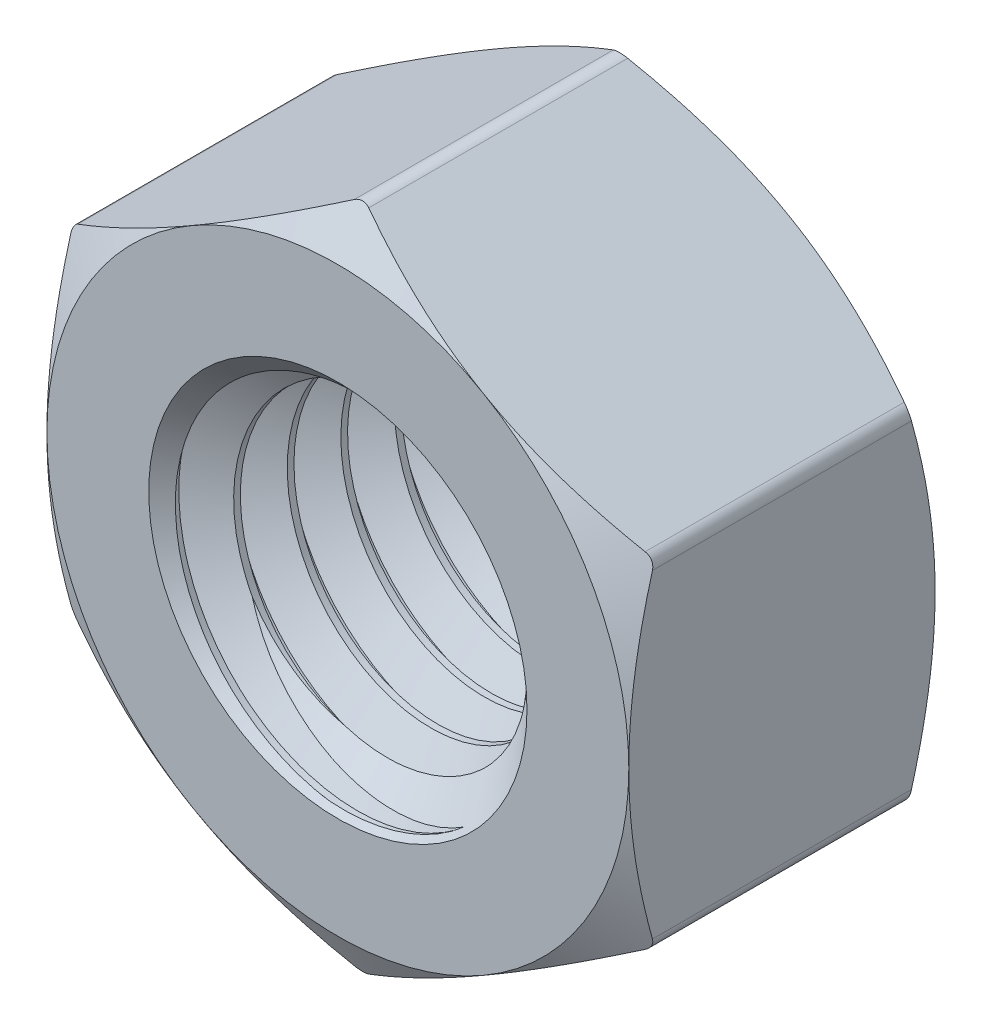
SolidWorks part; units mm, degrees
ref_plane "Front" through (0, 0, 0) normal (0, 0, 1) x (1, 0, 0)
ref_plane "Top" through (0, 0, 0) normal (0, 1, 0) x (1, 0, 0)
ref_plane "Right" through (0, 0, 0) normal (1, 0, 0) x (0, 0, -1)
sketch "Sketch1" plane through (0, 0, 0) normal (0, 0, 1) x (1, 0, 0)
  line L0 (0, 6) -> (0, 4.25) construction
  line L1 (-9.5, 5.4848) -> (-9.5, -5.4848)
  line L2 (-9.5, -5.4848) -> (0, -10.9697)
  line L3 (0, -10.9697) -> (9.5, -5.4848)
  line L4 (9.5, -5.4848) -> (9.5, 5.4848)
  line L5 (9.5, 5.4848) -> (0, 10.9697)
  line L6 (0, 10.9697) -> (-9.5, 5.4848)
  circle A0 centre (0, 0) radius 9.5 construction
  circle A1 centre (0, 0) radius 6 construction
  point P10 (0, 6)
  dimension "Width" = 19
  dimension "Thread Size" = 12
  dimension "Thread Pitch" = 1.75
sketch "Sketch2" plane through (0, 0, 0) normal (1, 0, 0) x (0, 0, -1)
  line L0 (-5, 0) -> (5, 0) construction
  line L1 (-5, 10.9697) -> (5, 10.9697) construction
  dimension "Height" = 10
sketch "Sketch15" plane through (0, 0, 0) normal (0, 0, 1) x (1, 0, 0)
  line L1 (0, 10.9697) -> (-9.5, 5.4848)
  line L2 (-9.5, 5.4848) -> (-9.5, -5.4848)
  line L3 (-9.5, -5.4848) -> (0, -10.9697)
  line L4 (0, -10.9697) -> (9.5, -5.4848)
  line L5 (9.5, -5.4848) -> (9.5, 5.4848)
  line L6 (9.5, 5.4848) -> (0, 10.9697)
  circle A0 centre (0, 0) radius 9.5 construction
extrude "Boss-Extrude2" add sketch "Sketch15" along normal mid plane 10
sketch "Sketch16" plane through (0, 0, 0) normal (0, 0, 1) x (1, 0, 0)
  circle A0 centre (0, 0) radius 6 construction
  circle A1 centre (0, 0) radius 6
sketch "Sketch4" plane through (0, 0, -5) normal (0, 0, -1) x (-1, 0, 0)
  circle A0 centre (0, 0) radius 6 construction
  circle A1 centre (0, 0) radius 6
extrude "Cut-Extrude4" cut sketch "Sketch16" against normal through all both and the other way through all
sketch "Sketch7" plane through (0, 0, 5) normal (0, 0, 1) x (1, 0, 0)
  circle A0 centre (0, 0) radius 9.5 construction
  circle A1 centre (0, 0) radius 9.5
extrude "Cut-Extrude5" cut sketch "Sketch7" against normal through all draft 60 flip side to cut
mirror "Mirror4" about plane through (0, 0, 0) normal (0, 0, 1) of "Cut-Extrude5"
fillet "Fillet2" radius 0.475 6 edges at (-9.5, 5.4848, 0) (-9.5, -5.4848, 0) (0, -10.9697, 0) (9.5, -5.4848, 0) (9.5, 5.4848, 0) (0, 10.9697, 0)
sketch "Sketch8" plane through (0, 0, 5) normal (0, 0, 1) x (1, 0, 0)
  line L0 (1.5529, -5.7956) -> (0, 0) construction
  line L2 (0, 6) -> (0, 4.25) construction
  circle A0 centre (0, 0) radius 6 construction
  point P0 (1.5529, -5.7956)
  dimension "D1" = 15
sketch "Sketch13" plane through (0, 0, -5) normal (0, 0, -1) x (-1, 0, 0)
  circle A0 centre (0, 0) radius 6 construction
  circle A1 centre (0, 0) radius 6
extrude "Boss-Extrude1" add sketch "Sketch13" against normal up to surface (10 mm away) separate body up to face at (6, 0, 5)
curve "Helix/Spiral3" pitch 1.75 height 13.5 radius 6 centre (0, 0, -5) axis (0, 0, 1) start towards (0, 1, 0)
sketch "Sketch12" plane through (0, 0, 0) normal (1, 0, 0) x (0, 0, -1)
  line L0 (6.5312, 6) -> (5, 6)
  line L1 (6.5312, 6) -> (5.875, 4.8633)
  line L2 (5.875, 4.8633) -> (5.6562, 4.8633)
  line L3 (5.6562, 4.8633) -> (5, 6)
  line L4 (5.7656, 4.8633) -> (5.7656, 6) construction
  line L5 (5.3281, 5.4317) -> (6.2031, 5.4317) construction
  dimension "D1" = 60
  dimension "D2" = 0.2188
  dimension "D3" = 0.875
sweep "Cut-Sweep1" cut profiles "Sketch12" path "Helix/Spiral3" align with end faces yes
sketch "Sketch17" plane through (0, 0, 5) normal (0, 0, 1) x (1, 0, 0)
  circle A1 centre (0, 0) radius 6
  circle A2 centre (0, 0) radius 6
  dimension "D1" = 0
extrude "Boss-Extrude3" add sketch "Sketch17" against normal up to surface (10 mm away) up to face at (6, 0, -5)
combine bodies "Combine1" operation type subtract main body 127 bodies to subtract 118
sketch "Sketch10" plane through (0, 0, 5) normal (0, 0, 1) x (1, 0, 0)
  circle A0 centre (0, 0) radius 6 construction
  circle A1 centre (0, 0) radius 6 construction
  circle A2 centre (0, 0) radius 6.175
  dimension "D1" = 0.175
extrude "Cut-Extrude2" cut sketch "Sketch10" against normal through all draft 45
sketch "Sketch11" plane through (0, 0, -5) normal (0, 0, -1) x (-1, 0, 0)
  circle A1 centre (0, 0) radius 6.175 construction
  circle A2 centre (0, 0) radius 6.175
extrude "Cut-Extrude3" cut sketch "Sketch11" against normal through all draft 45
equation "\"D1\"= \"Height@Sketch2\""
equation "\"D3@Helix/Spiral3\"=\"Height@Sketch2\"+\"Thread Pitch@Sketch1\"*2"
equation "\"D4@Helix/Spiral3\"=\"Thread Pitch@Sketch1\""
equation "\"D2@Sketch12\" = \"D4@Helix/Spiral3\"*.125"
equation "\"D3@Sketch12\" = \"D4@Helix/Spiral3\"*.50"
equation "\"D1@Boss-Extrude2\"=\"Height@Sketch2\""
equation "\"D1@Fillet2\"=\"Width@Sketch1\"*0.025"
equation "\"D1@Sketch10\"=\"Thread Pitch@Sketch1\"*0.1"
